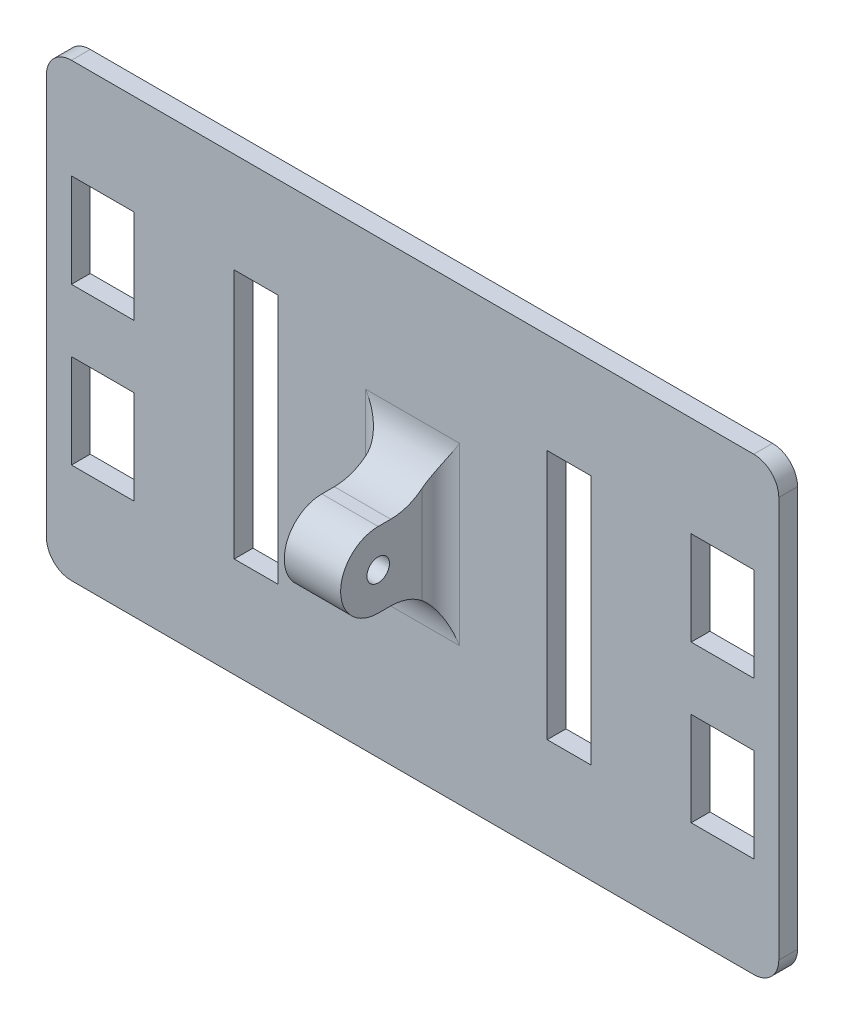
SolidWorks part; units mm, degrees
ref_plane "Front Plane" through (0, 0, 0) normal (0, 0, 1) x (1, 0, 0)
ref_plane "Top Plane" through (0, 0, 0) normal (0, 1, 0) x (1, 0, 0)
ref_plane "Right Plane" through (0, 0, 0) normal (1, 0, 0) x (0, 0, -1)
sketch "Sketch1" plane through (0, 0, 0) normal (0, 0, 1) x (1, 0, 0)
  line L1 (0, 0) -> (117, 0)
  line L2 (0, 0) -> (0, 72)
  line L3 (0, 72) -> (117, 72)
  line L4 (117, 0) -> (117, 72)
  dimension "D1" = 72
  dimension "D2" = 117
extrude "Boss-Extrude1" add sketch "Sketch1" along normal blind 3
fillet "Fillet1" radius 4 4 edges at (117, 72, 1.5) (0, 72, 1.5) (0, 0, 1.5) (117, 0, 1.5)
ref_plane "Plane1" through (58.5, 0, 0) normal (-1, 0, 0) x (0, 0, 1)
sketch "Sketch2" plane through (58.5, 0, 0) normal (-1, 0, 0) x (0, 0, 1)
  line L0 (3, 4) -> (3, 68) construction
  line L1 (3, 4) -> (3, 68) construction
  line L2 (3, 36) -> (23.0793, 36) construction
  line L3 (13, 30) -> (3, 30)
  line L4 (13, 42) -> (3, 42)
  line L5 (3, 30) -> (3, 42)
  circle A0 centre (13, 36) radius 1.8
  arc A1 (13, 30) -> (13, 42) centre (13, 36) ccw
  dimension "D1" = 3.6
  dimension "D2" = 12
  dimension "D3" = 10
extrude "Boss-Extrude2" add sketch "Sketch2" along normal mid plane 9
fillet "Fillet2" radius 8 2 edges at (58.5, 42, 3) (58.5, 30, 3)
fillet "Fillet3" radius 3 2 edges at (54, 36, 3) (63, 36, 3)
sketch "Sketch3" plane through (0, 0, 0) normal (0, 0, -1) x (-1, 0, 0)
  line L0 (-58.5, 114) -> (-58.5, 0) construction
  line L1 (-113, 72) -> (-4, 72) construction
  line L2 (-4, 0) -> (-113, 0) construction
  line L3 (-63.5, 68) -> (-63.5, 58)
  line L4 (-78.5, 68) -> (-78.5, 58)
  line L5 (-78.5, 68) -> (-63.5, 68)
  line L6 (-78.5, 4) -> (-63.5, 4)
  line L7 (-38.5, 4) -> (-53.5, 4)
  line L8 (-38.5, 68) -> (-53.5, 68)
  line L9 (-53.5, 68) -> (-53.5, 58)
  line L10 (-38.5, 68) -> (-38.5, 58)
  line L11 (-78.5, 58) -> (-63.5, 58)
  line L12 (-78.5, 14) -> (-63.5, 14)
  line L13 (-53.5, 58) -> (-38.5, 58)
  line L14 (-78.5, 14) -> (-78.5, 4)
  line L15 (-63.5, 14) -> (-63.5, 4)
  line L16 (-53.5, 14) -> (-53.5, 4)
  line L17 (-38.5, 14) -> (-38.5, 4)
  line L18 (-53.5, 14) -> (-38.5, 14)
  line L19 (-78.5, 42) -> (-38.5, 42)
  line L20 (-38.5, 42) -> (-38.5, 35)
  line L21 (-38.5, 35) -> (-78.5, 35)
  line L22 (-78.5, 35) -> (-78.5, 42)
  line L23 (-117, 36) -> (0, 36) construction
  line L24 (-117, 4) -> (-117, 68) construction
  line L25 (0, 68) -> (0, 4) construction
  line L26 (-78.5, 37) -> (-78.5, 30)
  line L27 (-38.5, 37) -> (-78.5, 37)
  line L28 (-38.5, 30) -> (-38.5, 37)
  line L29 (-78.5, 30) -> (-38.5, 30)
  dimension "D1" = 4
  dimension "D2" = 4
  dimension "D3" = 10
  dimension "D4" = 15
  dimension "D5" = 10
  dimension "D6" = 10
  dimension "D7" = 16
  dimension "D8" = 7
sketch "Sketch4" plane through (0, 0, 0) normal (0, 0, -1) x (-1, 0, 0)
  line L0 (-117, 36) -> (0, 36) construction
  line L1 (-117, 4) -> (-117, 68) construction
  line L2 (0, 68) -> (0, 4) construction
  line L3 (-58.5, 72) -> (-58.5, 0) construction
  line L4 (-113, 72) -> (-4, 72) construction
  line L5 (-4, 0) -> (-113, 0) construction
  line L6 (-30, 16) -> (-37, 56) construction
  line L7 (-113, 56) -> (-103, 56)
  line L8 (-113, 56) -> (-113, 41)
  line L9 (-113, 41) -> (-103, 41)
  line L10 (-103, 56) -> (-103, 41)
  line L11 (-113, 56) -> (-103, 41) construction
  line L12 (-113, 41) -> (-103, 56) construction
  line L13 (-113, 31) -> (-103, 31)
  line L14 (-113, 31) -> (-113, 16)
  line L15 (-113, 16) -> (-103, 16)
  line L16 (-103, 31) -> (-103, 16)
  line L17 (-113, 31) -> (-103, 16) construction
  line L18 (-113, 16) -> (-103, 31) construction
  line L19 (-87, 56) -> (-80, 56)
  line L20 (-87, 56) -> (-87, 16)
  line L21 (-87, 16) -> (-80, 16)
  line L22 (-80, 56) -> (-80, 16)
  line L23 (-87, 56) -> (-80, 16) construction
  line L24 (-87, 16) -> (-80, 56) construction
  line L25 (-30, 56) -> (-37, 16) construction
  line L26 (-4, 16) -> (-14, 31) construction
  line L27 (-4, 31) -> (-14, 16) construction
  line L28 (-4, 41) -> (-14, 56) construction
  line L29 (-4, 56) -> (-14, 41) construction
  line L30 (-37, 56) -> (-37, 16)
  line L31 (-30, 16) -> (-37, 16)
  line L32 (-30, 56) -> (-30, 16)
  line L33 (-30, 56) -> (-37, 56)
  line L34 (-14, 31) -> (-14, 16)
  line L35 (-4, 16) -> (-14, 16)
  line L36 (-4, 31) -> (-4, 16)
  line L37 (-4, 31) -> (-14, 31)
  line L38 (-14, 56) -> (-14, 41)
  line L39 (-4, 41) -> (-14, 41)
  line L40 (-4, 56) -> (-4, 41)
  line L41 (-4, 56) -> (-14, 56)
  point P16 (-108, 48.5)
  point P21 (-108, 23.5)
  point P26 (-83.5, 36)
  point P27 (-108, 41)
  point P28 (-108, 31)
  point P41 (-33.5, 36)
  point P42 (-9, 23.5)
  point P43 (-9, 48.5)
  dimension "D1" = 10
  dimension "D2" = 10
  dimension "D3" = 15
  dimension "D4" = 16
  dimension "D5" = 7
  dimension "D6" = 4
extrude "Cut-Extrude3" cut sketch "Sketch4" against normal up to next
extrude "Cut-Extrude2" cut sketch "Sketch3" against normal blind 10 rebuild error yes
